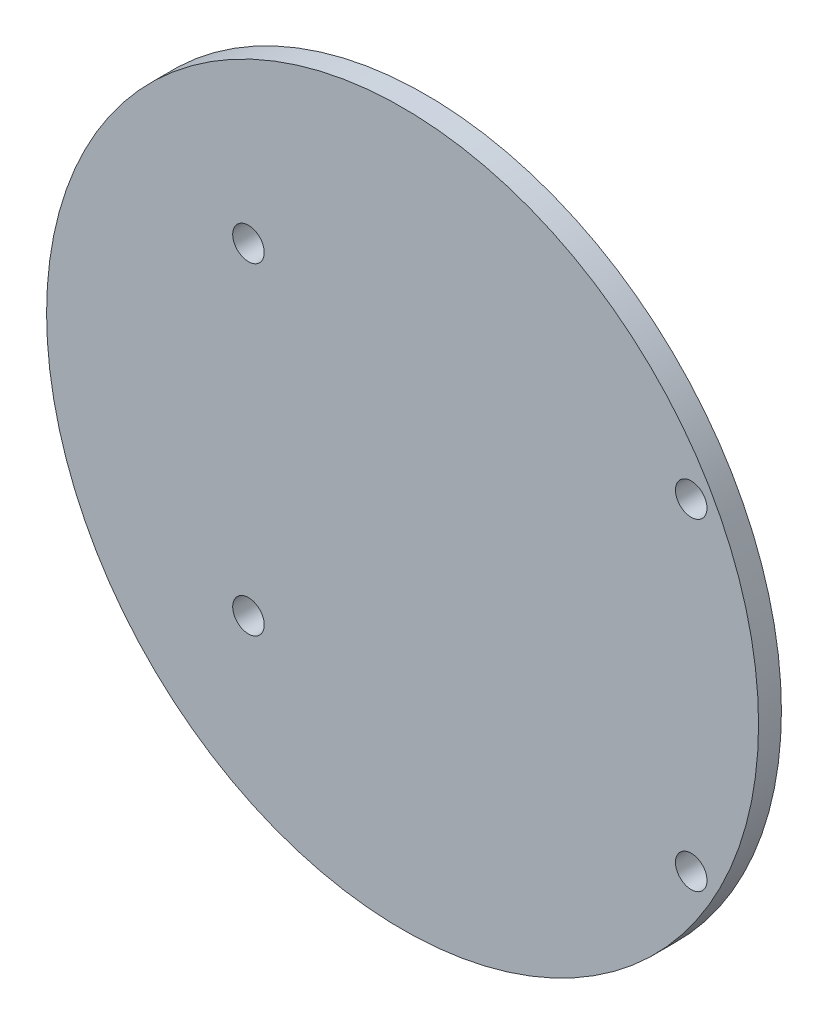
SolidWorks part; units mm, degrees
ref_plane "Front Plane" through (0, 0, 0) normal (0, 0, 1) x (1, 0, 0)
ref_plane "Top Plane" through (0, 0, 0) normal (0, 1, 0) x (1, 0, 0)
ref_plane "Right Plane" through (0, 0, 0) normal (1, 0, 0) x (0, 0, -1)
sketch "Sketch1" plane through (0, 0, 0) normal (0, 0, 1) x (1, 0, 0)
  circle A0 centre (27.94, 27.94) radius 25.527
  dimension "D1" = 51.054
extrude "BOARD" add sketch "Sketch1" along normal blind 1.64 separate body
sketch "Sketch2" plane through (0, 0, 0) normal (0, 0, 1) x (1, 0, 0)
  circle A0 centre (48.64, 39.5) radius 1.13
  circle A1 centre (48.64, 16.38) radius 1.13
  circle A2 centre (16.89, 39.5) radius 1.13
  circle A3 centre (16.89, 16.38) radius 1.13
extrude "NON-PLATED HOLES" cut sketch "Sketch2" along normal through all
ref_plane "Plane1" through (0, 0, 2.4) normal (0, 0, 1) x (1, 0, 0)
